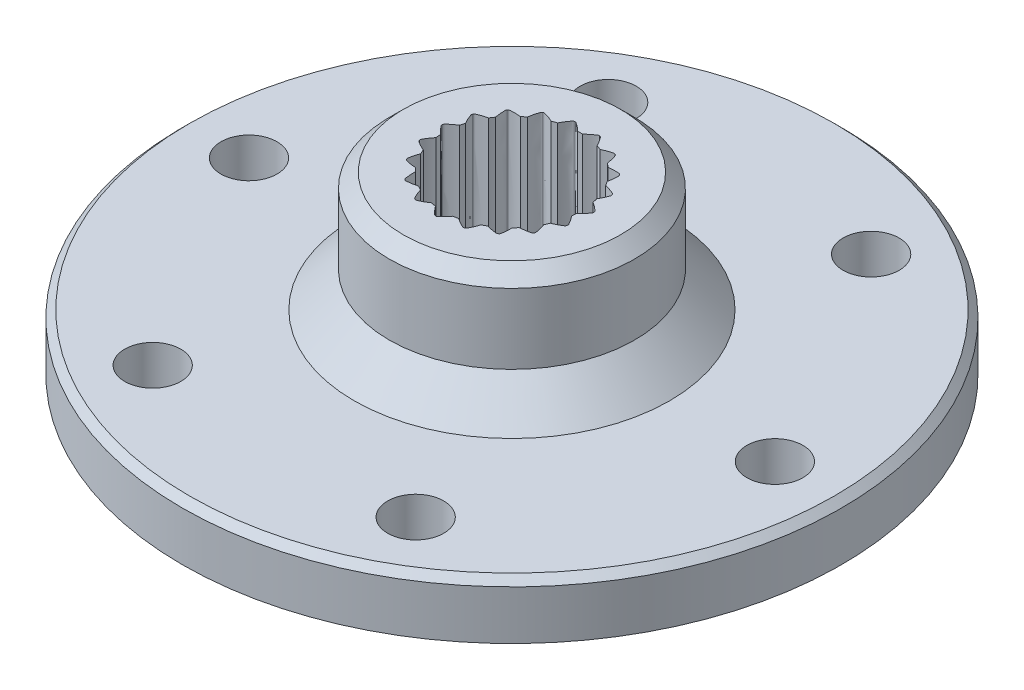
SolidWorks part; units mm, degrees
material "AISI 4340 Steel, normalized"
ref_plane "Front Plane" through (0, 0, 0) normal (0, 0, 1) x (1, 0, 0)
ref_plane "Top Plane" through (0, 0, 0) normal (0, 1, 0) x (1, 0, 0)
ref_plane "Right Plane" through (0, 0, 0) normal (1, 0, 0) x (0, 0, -1)
sketch "Sketch1" plane through (0, 0, 0) normal (0, 1, 0) x (1, 0, 0)
  circle A8 centre (0, 0) radius 47
  circle A9 centre (0, 0) radius 28
  circle A11 centre (-18.75, -32.476) radius 4.55
  circle A12 centre (18.75, -32.476) radius 4.55
  circle A13 centre (37.5, 0) radius 4.55
  circle A14 centre (18.75, 32.476) radius 4.55
  circle A15 centre (-18.75, 32.476) radius 4.55
  circle A16 centre (-37.5, 0) radius 4.55
  circle A17 centre (0, 0) radius 37.5 construction
  dimension "D1" = 94
  dimension "D2" = 56
  dimension "D3" = 9.1
  dimension "D5" = 75
  dimension "D4" = 18.75
extrude "Boss-Extrude1" add sketch "Sketch1" along normal blind 8 contours A9 | A8 A16 A15 A14 A13 A12 A11 A9 | A15 | A14 | A13 | A12 | A11 | A16 region at (-45.6706, 0, 0) region at (0, 0, 0) region at (-18.75, 0, 32.476) region at (18.75, 0, 32.476) region at (37.5, 0, 0) region at (18.75, 0, -32.476) region at (-18.75, 0, -32.476)
sketch "Sketch17" plane through (0, 8, 0) normal (0, 1, 0) x (1, 0, 0)
  circle A0 centre (-18.75, -32.476) radius 4.55
  circle A1 centre (18.75, -32.476) radius 4.55
  circle A2 centre (37.5, 0) radius 4.55
  circle A3 centre (18.75, 32.476) radius 4.55
  circle A4 centre (-18.75, 32.476) radius 4.55
  circle A5 centre (-37.5, 0) radius 4.55
  circle A6 centre (0, 0) radius 37.5 construction
  circle A7 centre (0, 0) radius 47 construction
  point P1 (-37.5, 0)
  point P2 (-18.75, -32.476)
  point P3 (18.75, -32.476)
  point P4 (37.5, 0)
  point P5 (18.75, 32.476)
  point P6 (-18.75, 32.476)
  dimension "D1" = 9.1
  dimension "D2" = 75
  dimension "D3" = 18.75
  dimension "D4" = 37.5
hole_wizard "Ø8.0mm Dowel Hole1" positions "Sketch17" profile "Sketch18" hole size "Ø8.0" standard "DIN" end condition through all
sketch "Sketch18" plane through (-18.75, 8, -32.476) normal (1, 0, 0) x (0, 0, 1)
  line L0 (0, 0) -> (0, 8)
  line L1 (0, 8) -> (4, 8)
  line L2 (4, 8) -> (4, 0)
  line L5 (4, 0) -> (0, 0)
  line L11 (0, -6.35) -> (0, 107.95) construction
  dimension "Thru Hole Dia." = 8
  dimension "Thru Hole Depth" = 8
sketch "Sketch12" plane through (0, 8, 0) normal (0, 1, 0) x (1, 0, 0)
  circle A0 centre (0, 0) radius 17.5
  dimension "D1" = 35
extrude "Boss-Extrude5" add sketch "Sketch12" along normal blind 17 contours A0
sketch "Sketch13" plane through (0, 0, 0) normal (0, -1, 0) x (1, 0, 0)
  circle A0 centre (0, 0) radius 28
  dimension "D1" = 56
extrude "Boss-Extrude6" add sketch "Sketch13" along normal blind 5.08
sketch "Sketch16" plane through (0, 0, 0) normal (0, 1, 0) x (1, 0, 0)
  line B0 (1.8668, 11.187) -> (2.1421, 11.1376)
  line B1 (2.1421, 11.1376) -> (2.416, 11.0814)
  line B2 (2.416, 11.0814) -> (2.491, 11.1676)
  line B3 (2.491, 11.1676) -> (2.5708, 11.2556)
  line B4 (2.5708, 11.2556) -> (2.6534, 11.343)
  line B5 (2.6534, 11.343) -> (2.7388, 11.4297)
  line B6 (2.7388, 11.4297) -> (2.8266, 11.5155)
  line B7 (2.8266, 11.5155) -> (2.9189, 11.6021)
  line B8 (2.9189, 11.6021) -> (3.0133, 11.6874)
  line B9 (3.0133, 11.6874) -> (3.1122, 11.7733)
  line B10 (3.1122, 11.7733) -> (3.2129, 11.8575)
  line B11 (3.2129, 11.8575) -> (3.3178, 11.942)
  line B12 (3.3178, 11.942) -> (3.4243, 12.0245)
  line B13 (3.4243, 12.0245) -> (3.5292, 12.1028)
  line B14 (3.5292, 12.1028) -> (3.5601, 12.1214)
  line B15 (3.5601, 12.1214) -> (3.594, 12.1339)
  line B16 (3.594, 12.1339) -> (3.6296, 12.14)
  line B17 (3.6296, 12.14) -> (3.6657, 12.1394)
  line B18 (3.6657, 12.1394) -> (3.701, 12.1321)
  line B19 (3.701, 12.1321) -> (3.9104, 12.0662)
  line B20 (3.9104, 12.0662) -> (4.1185, 11.9968)
  line B21 (4.1185, 11.9968) -> (4.3254, 11.9237)
  line B22 (4.3254, 11.9237) -> (4.531, 11.8471)
  line B23 (4.531, 11.8471) -> (4.5634, 11.8312)
  line B24 (4.5634, 11.8312) -> (4.5923, 11.8095)
  line B25 (4.5923, 11.8095) -> (4.6167, 11.7829)
  line B26 (4.6167, 11.7829) -> (4.6357, 11.7522)
  line B27 (4.6357, 11.7522) -> (4.6487, 11.7185)
  line B28 (4.6487, 11.7185) -> (4.6833, 11.5923)
  line B29 (4.6833, 11.5923) -> (4.7167, 11.4617)
  line B30 (4.7167, 11.4617) -> (4.7476, 11.3306)
  line B31 (4.7476, 11.3306) -> (4.7754, 11.2023)
  line B32 (4.7754, 11.2023) -> (4.8006, 11.0738)
  line B33 (4.8006, 11.0738) -> (4.8228, 10.9485)
  line B34 (4.8228, 10.9485) -> (4.8424, 10.8235)
  line B35 (4.8424, 10.8235) -> (4.859, 10.7019)
  line B36 (4.859, 10.7019) -> (4.8731, 10.581)
  line B37 (4.8731, 10.581) -> (4.8846, 10.4612)
  line B38 (4.8846, 10.4612) -> (4.8935, 10.3428)
  line B39 (4.8935, 10.3428) -> (4.8997, 10.2287)
  line B40 (4.8997, 10.2287) -> (5.1505, 10.1048)
  line B41 (5.1505, 10.1048) -> (5.398, 9.9747)
  line B42 (5.398, 9.9747) -> (5.6424, 9.8386)
  line B43 (5.6424, 9.8386) -> (5.8832, 9.6965)
  line B44 (5.8832, 9.6965) -> (5.9822, 9.7537)
  line B45 (5.9822, 9.7537) -> (6.0861, 9.811)
  line B46 (6.0861, 9.811) -> (6.1927, 9.8669)
  line B47 (6.1927, 9.8669) -> (6.3016, 9.9212)
  line B48 (6.3016, 9.9212) -> (6.4125, 9.9737)
  line B49 (6.4125, 9.9737) -> (6.5279, 10.0257)
  line B50 (6.5279, 10.0257) -> (6.645, 10.0757)
  line B51 (6.645, 10.0757) -> (6.7663, 10.1248)
  line B52 (6.7663, 10.1248) -> (6.8889, 10.1718)
  line B53 (6.8889, 10.1718) -> (7.0156, 10.2176)
  line B54 (7.0156, 10.2176) -> (7.1431, 10.2611)
  line B55 (7.1431, 10.2611) -> (7.2677, 10.3012)
  line B56 (7.2677, 10.3012) -> (7.303, 10.3087)
  line B57 (7.303, 10.3087) -> (7.3391, 10.3095)
  line B58 (7.3391, 10.3095) -> (7.3748, 10.3037)
  line B59 (7.3748, 10.3037) -> (7.4087, 10.2914)
  line B60 (7.4087, 10.2914) -> (7.4398, 10.273)
  line B61 (7.4398, 10.273) -> (7.6164, 10.1428)
  line B62 (7.6164, 10.1428) -> (7.7907, 10.0095)
  line B63 (7.7907, 10.0095) -> (7.9627, 9.8732)
  line B64 (7.9627, 9.8732) -> (8.1323, 9.734)
  line B65 (8.1323, 9.734) -> (8.1577, 9.7084)
  line B66 (8.1577, 9.7084) -> (8.178, 9.6785)
  line B67 (8.178, 9.6785) -> (8.1924, 9.6454)
  line B68 (8.1924, 9.6454) -> (8.2004, 9.6102)
  line B69 (8.2004, 9.6102) -> (8.2018, 9.5741)
  line B70 (8.2018, 9.5741) -> (8.1936, 9.4435)
  line B71 (8.1936, 9.4435) -> (8.1827, 9.3092)
  line B72 (8.1827, 9.3092) -> (8.1694, 9.1751)
  line B73 (8.1694, 9.1751) -> (8.154, 9.0448)
  line B74 (8.154, 9.0448) -> (8.1362, 8.9151)
  line B75 (8.1362, 8.9151) -> (8.1164, 8.7894)
  line B76 (8.1164, 8.7894) -> (8.0944, 8.6647)
  line B77 (8.0944, 8.6647) -> (8.0706, 8.5443)
  line B78 (8.0706, 8.5443) -> (8.0447, 8.4254)
  line B79 (8.0447, 8.4254) -> (8.0167, 8.3084)
  line B80 (8.0167, 8.3084) -> (7.9867, 8.1935)
  line B81 (7.9867, 8.1935) -> (7.9555, 8.0835)
  line B82 (7.9555, 8.0835) -> (8.1524, 7.8849)
  line B83 (8.1524, 7.8849) -> (8.3443, 7.6815)
  line B84 (8.3443, 7.6815) -> (8.5312, 7.4734)
  line B85 (8.5312, 7.4734) -> (8.7129, 7.2608)
  line B86 (8.7129, 7.2608) -> (8.8251, 7.2828)
  line B87 (8.8251, 7.2828) -> (8.942, 7.3032)
  line B88 (8.942, 7.3032) -> (9.061, 7.3215)
  line B89 (9.061, 7.3215) -> (9.1816, 7.3375)
  line B90 (9.1816, 7.3375) -> (9.3035, 7.3512)
  line B91 (9.3035, 7.3512) -> (9.4296, 7.3629)
  line B92 (9.4296, 7.3629) -> (9.5565, 7.3722)
  line B93 (9.5565, 7.3722) -> (9.6872, 7.3792)
  line B94 (9.6872, 7.3792) -> (9.8184, 7.3838)
  line B95 (9.8184, 7.3838) -> (9.9531, 7.386)
  line B96 (9.9531, 7.386) -> (10.0879, 7.3858)
  line B97 (10.0879, 7.3858) -> (10.2187, 7.3832)
  line B98 (10.2187, 7.3832) -> (10.2546, 7.3788)
  line B99 (10.2546, 7.3788) -> (10.289, 7.3679)
  line B100 (10.289, 7.3679) -> (10.3208, 7.3508)
  line B101 (10.3208, 7.3508) -> (10.3489, 7.3282)
  line B102 (10.3489, 7.3282) -> (10.3723, 7.3007)
  line B103 (10.3723, 7.3007) -> (10.4971, 7.1202)
  line B104 (10.4971, 7.1202) -> (10.6187, 6.9375)
  line B105 (10.6187, 6.9375) -> (10.7371, 6.7528)
  line B106 (10.7371, 6.7528) -> (10.8523, 6.566)
  line B107 (10.8523, 6.566) -> (10.868, 6.5336)
  line B108 (10.868, 6.5336) -> (10.8775, 6.4987)
  line B109 (10.8775, 6.4987) -> (10.8804, 6.4627)
  line B110 (10.8804, 6.4627) -> (10.8765, 6.4268)
  line B111 (10.8765, 6.4268) -> (10.8661, 6.3922)
  line B112 (10.8661, 6.3922) -> (10.8159, 6.2714)
  line B113 (10.8159, 6.2714) -> (10.7621, 6.1479)
  line B114 (10.7621, 6.1479) -> (10.7059, 6.0254)
  line B115 (10.7059, 6.0254) -> (10.649, 5.9071)
  line B116 (10.649, 5.9071) -> (10.59, 5.7902)
  line B117 (10.59, 5.7902) -> (10.5305, 5.6777)
  line B118 (10.5305, 5.6777) -> (10.4692, 5.567)
  line B119 (10.4692, 5.567) -> (10.4077, 5.4608)
  line B120 (10.4077, 5.4608) -> (10.3446, 5.3568)
  line B121 (10.3446, 5.3568) -> (10.2801, 5.2552)
  line B122 (10.2801, 5.2552) -> (10.2144, 5.1563)
  line B123 (10.2144, 5.1563) -> (10.1492, 5.0624)
  line B124 (10.1492, 5.0624) -> (10.2709, 4.8106)
  line B125 (10.2709, 4.8106) -> (10.3864, 4.5559)
  line B126 (10.3864, 4.5559) -> (10.4956, 4.2984)
  line B127 (10.4956, 4.2984) -> (10.5984, 4.0383)
  line B128 (10.5984, 4.0383) -> (10.7116, 4.0227)
  line B129 (10.7116, 4.0227) -> (10.8289, 4.0041)
  line B130 (10.8289, 4.0041) -> (10.9473, 3.9827)
  line B131 (10.9473, 3.9827) -> (11.0666, 3.9587)
  line B132 (11.0666, 3.9587) -> (11.1864, 3.932)
  line B133 (11.1864, 3.932) -> (11.3094, 3.9022)
  line B134 (11.3094, 3.9022) -> (11.4324, 3.8697)
  line B135 (11.4324, 3.8697) -> (11.5584, 3.834)
  line B136 (11.5584, 3.834) -> (11.684, 3.7957)
  line B137 (11.684, 3.7957) -> (11.8121, 3.7541)
  line B138 (11.8121, 3.7541) -> (11.9394, 3.7101)
  line B139 (11.9394, 3.7101) -> (12.0624, 3.6651)
  line B140 (12.0624, 3.6651) -> (12.0948, 3.6494)
  line B141 (12.0948, 3.6494) -> (12.1238, 3.6279)
  line B142 (12.1238, 3.6279) -> (12.1484, 3.6014)
  line B143 (12.1484, 3.6014) -> (12.1676, 3.5708)
  line B144 (12.1676, 3.5708) -> (12.1808, 3.5372)
  line B145 (12.1808, 3.5372) -> (12.2402, 3.326)
  line B146 (12.2402, 3.326) -> (12.2959, 3.1137)
  line B147 (12.2959, 3.1137) -> (12.3479, 2.9006)
  line B148 (12.3479, 2.9006) -> (12.3963, 2.6865)
  line B149 (12.3963, 2.6865) -> (12.4006, 2.6507)
  line B150 (12.4006, 2.6507) -> (12.3983, 2.6147)
  line B151 (12.3983, 2.6147) -> (12.3893, 2.5797)
  line B152 (12.3893, 2.5797) -> (12.374, 2.547)
  line B153 (12.374, 2.547) -> (12.3529, 2.5177)
  line B154 (12.3529, 2.5177) -> (12.2662, 2.4196)
  line B155 (12.2662, 2.4196) -> (12.1752, 2.3203)
  line B156 (12.1752, 2.3203) -> (12.0823, 2.2227)
  line B157 (12.0823, 2.2227) -> (11.9901, 2.1293)
  line B158 (11.9901, 2.1293) -> (11.8963, 2.0379)
  line B159 (11.8963, 2.0379) -> (11.8035, 1.9508)
  line B160 (11.8035, 1.9508) -> (11.7096, 1.866)
  line B161 (11.7096, 1.866) -> (11.6169, 1.7856)
  line B162 (11.6169, 1.7856) -> (11.5234, 1.7077)
  line B163 (11.5234, 1.7077) -> (11.4294, 1.6325)
  line B164 (11.4294, 1.6325) -> (11.3352, 1.5603)
  line B165 (11.3352, 1.5603) -> (11.243, 1.4927)
  line B166 (11.243, 1.4927) -> (11.2764, 1.215)
  line B167 (11.2764, 1.215) -> (11.3029, 0.9366)
  line B168 (11.3029, 0.9366) -> (11.3226, 0.6576)
  line B169 (11.3226, 0.6576) -> (11.3354, 0.3782)
  line B170 (11.3354, 0.3782) -> (11.4374, 0.3267)
  line B171 (11.4374, 0.3267) -> (11.5422, 0.271)
  line B172 (11.5422, 0.271) -> (11.6473, 0.2123)
  line B173 (11.6473, 0.2123) -> (11.7523, 0.1509)
  line B174 (11.7523, 0.1509) -> (11.857, 0.0868)
  line B175 (11.857, 0.0868) -> (11.9636, 0.0186)
  line B176 (11.9636, 0.0186) -> (12.0695, -0.0521)
  line B177 (12.0695, -0.0521) -> (12.177, -0.1268)
  line B178 (12.177, -0.1268) -> (12.2834, -0.2037)
  line B179 (12.2834, -0.2037) -> (12.391, -0.2847)
  line B180 (12.391, -0.2847) -> (12.4972, -0.3677)
  line B181 (12.4972, -0.3677) -> (12.5988, -0.4501)
  line B182 (12.5988, -0.4501) -> (12.6245, -0.4756)
  line B183 (12.6245, -0.4756) -> (12.6449, -0.5053)
  line B184 (12.6449, -0.5053) -> (12.6595, -0.5383)
  line B185 (12.6595, -0.5383) -> (12.6678, -0.5735)
  line B186 (12.6678, -0.5735) -> (12.6694, -0.6096)
  line B187 (12.6694, -0.6096) -> (12.6569, -0.8286)
  line B188 (12.6569, -0.8286) -> (12.6407, -1.0474)
  line B189 (12.6407, -1.0474) -> (12.6207, -1.2659)
  line B190 (12.6207, -1.2659) -> (12.5969, -1.4841)
  line B191 (12.5969, -1.4841) -> (12.5894, -1.5194)
  line B192 (12.5894, -1.5194) -> (12.5755, -1.5527)
  line B193 (12.5755, -1.5527) -> (12.5556, -1.5829)
  line B194 (12.5556, -1.5829) -> (12.5305, -1.6088)
  line B195 (12.5305, -1.6088) -> (12.5011, -1.6297)
  line B196 (12.5011, -1.6297) -> (12.3872, -1.6943)
  line B197 (12.3872, -1.6943) -> (12.2689, -1.7587)
  line B198 (12.2689, -1.7587) -> (12.1494, -1.8208)
  line B199 (12.1494, -1.8208) -> (12.0318, -1.8792)
  line B200 (12.0318, -1.8792) -> (11.9135, -1.9352)
  line B201 (11.9135, -1.9352) -> (11.7974, -1.9875)
  line B202 (11.7974, -1.9875) -> (11.681, -2.0372)
  line B203 (11.681, -2.0372) -> (11.5672, -2.0832)
  line B204 (11.5672, -2.0832) -> (11.4535, -2.1265)
  line B205 (11.4535, -2.1265) -> (11.3402, -2.1671)
  line B206 (11.3402, -2.1671) -> (11.2277, -2.2048)
  line B207 (11.2277, -2.2048) -> (11.1185, -2.2388)
  line B208 (11.1185, -2.2388) -> (11.0599, -2.5123)
  line B209 (11.0599, -2.5123) -> (10.9946, -2.7842)
  line B210 (10.9946, -2.7842) -> (10.9226, -3.0545)
  line B211 (10.9226, -3.0545) -> (10.844, -3.3229)
  line B212 (10.844, -3.3229) -> (10.9238, -3.4047)
  line B213 (10.9238, -3.4047) -> (11.0048, -3.4915)
  line B214 (11.0048, -3.4915) -> (11.0852, -3.5811)
  line B215 (11.0852, -3.5811) -> (11.1645, -3.6733)
  line B216 (11.1645, -3.6733) -> (11.2427, -3.7679)
  line B217 (11.2427, -3.7679) -> (11.3214, -3.867)
  line B218 (11.3214, -3.867) -> (11.3986, -3.9682)
  line B219 (11.3986, -3.9682) -> (11.4761, -4.0738)
  line B220 (11.4761, -4.0738) -> (11.5517, -4.1811)
  line B221 (11.5517, -4.1811) -> (11.6272, -4.2927)
  line B222 (11.6272, -4.2927) -> (11.7007, -4.4056)
  line B223 (11.7007, -4.4056) -> (11.7701, -4.5165)
  line B224 (11.7701, -4.5165) -> (11.786, -4.5489)
  line B225 (11.786, -4.5489) -> (11.7957, -4.5837)
  line B226 (11.7957, -4.5837) -> (11.7988, -4.6197)
  line B227 (11.7988, -4.6197) -> (11.7952, -4.6556)
  line B228 (11.7952, -4.6556) -> (11.785, -4.6903)
  line B229 (11.785, -4.6903) -> (11.7021, -4.8934)
  line B230 (11.7021, -4.8934) -> (11.6157, -5.0951)
  line B231 (11.6157, -5.0951) -> (11.5258, -5.2953)
  line B232 (11.5258, -5.2953) -> (11.4325, -5.4939)
  line B233 (11.4325, -5.4939) -> (11.4139, -5.5248)
  line B234 (11.4139, -5.5248) -> (11.3899, -5.5518)
  line B235 (11.3899, -5.5518) -> (11.3614, -5.5739)
  line B236 (11.3614, -5.5739) -> (11.3292, -5.5903)
  line B237 (11.3292, -5.5903) -> (11.2946, -5.6005)
  line B238 (11.2946, -5.6005) -> (11.1659, -5.6246)
  line B239 (11.1659, -5.6246) -> (11.0331, -5.6471)
  line B240 (11.0331, -5.6471) -> (10.8998, -5.6671)
  line B241 (10.8998, -5.6671) -> (10.7697, -5.6841)
  line B242 (10.7697, -5.6841) -> (10.6396, -5.6987)
  line B243 (10.6396, -5.6987) -> (10.5129, -5.7104)
  line B244 (10.5129, -5.7104) -> (10.3866, -5.7196)
  line B245 (10.3866, -5.7196) -> (10.2641, -5.7262)
  line B246 (10.2641, -5.7262) -> (10.1425, -5.7302)
  line B247 (10.1425, -5.7302) -> (10.0221, -5.7318)
  line B248 (10.0221, -5.7318) -> (9.9034, -5.7309)
  line B249 (9.9034, -5.7309) -> (9.7892, -5.7277)
  line B250 (9.7892, -5.7277) -> (9.6449, -5.9673)
  line B251 (9.6449, -5.9673) -> (9.4949, -6.2033)
  line B252 (9.4949, -6.2033) -> (9.339, -6.4355)
  line B253 (9.339, -6.4355) -> (9.1775, -6.6639)
  line B254 (9.1775, -6.6639) -> (9.2264, -6.7672)
  line B255 (9.2264, -6.7672) -> (9.2749, -6.8755)
  line B256 (9.2749, -6.8755) -> (9.3218, -6.9864)
  line B257 (9.3218, -6.9864) -> (9.3669, -7.0994)
  line B258 (9.3669, -7.0994) -> (9.4101, -7.2142)
  line B259 (9.4101, -7.2142) -> (9.4524, -7.3336)
  line B260 (9.4524, -7.3336) -> (9.4926, -7.4543)
  line B261 (9.4926, -7.4543) -> (9.5315, -7.5793)
  line B262 (9.5315, -7.5793) -> (9.5682, -7.7054)
  line B263 (9.5682, -7.7054) -> (9.6034, -7.8354)
  line B264 (9.6034, -7.8354) -> (9.6362, -7.9661)
  line B265 (9.6362, -7.9661) -> (9.6658, -8.0936)
  line B266 (9.6658, -8.0936) -> (9.6704, -8.1294)
  line B267 (9.6704, -8.1294) -> (9.6682, -8.1654)
  line B268 (9.6682, -8.1654) -> (9.6595, -8.2005)
  line B269 (9.6595, -8.2005) -> (9.6444, -8.2333)
  line B270 (9.6444, -8.2333) -> (9.6235, -8.2627)
  line B271 (9.6235, -8.2627) -> (9.4792, -8.428)
  line B272 (9.4792, -8.428) -> (9.332, -8.5907)
  line B273 (9.332, -8.5907) -> (9.182, -8.7508)
  line B274 (9.182, -8.7508) -> (9.0292, -8.9083)
  line B275 (9.0292, -8.9083) -> (9.0016, -8.9316)
  line B276 (9.0016, -8.9316) -> (8.9701, -8.9493)
  line B277 (8.9701, -8.9493) -> (8.9359, -8.9609)
  line B278 (8.9359, -8.9609) -> (8.9002, -8.966)
  line B279 (8.9002, -8.966) -> (8.8641, -8.9644)
  line B280 (8.8641, -8.9644) -> (8.7346, -8.9454)
  line B281 (8.7346, -8.9454) -> (8.6017, -8.9235)
  line B282 (8.6017, -8.9235) -> (8.4692, -8.8992)
  line B283 (8.4692, -8.8992) -> (8.3405, -8.8731)
  line B284 (8.3405, -8.8731) -> (8.2127, -8.8446)
  line B285 (8.2127, -8.8446) -> (8.0891, -8.8145)
  line B286 (8.0891, -8.8145) -> (7.9667, -8.7822)
  line B287 (7.9667, -8.7822) -> (7.8486, -8.7486)
  line B288 (7.8486, -8.7486) -> (7.7323, -8.713)
  line B289 (7.7323, -8.713) -> (7.618, -8.6754)
  line B290 (7.618, -8.6754) -> (7.506, -8.6361)
  line B291 (7.506, -8.6361) -> (7.399, -8.5959)
  line B292 (7.399, -8.5959) -> (7.1848, -8.7757)
  line B293 (7.1848, -8.7757) -> (6.9662, -8.9502)
  line B294 (6.9662, -8.9502) -> (6.7434, -9.1192)
  line B295 (6.7434, -9.1192) -> (6.5165, -9.2827)
  line B296 (6.5165, -9.2827) -> (6.5292, -9.3963)
  line B297 (6.5292, -9.3963) -> (6.5399, -9.5146)
  line B298 (6.5399, -9.5146) -> (6.5482, -9.6346)
  line B299 (6.5482, -9.6346) -> (6.5542, -9.7561)
  line B300 (6.5542, -9.7561) -> (6.5578, -9.8788)
  line B301 (6.5578, -9.8788) -> (6.559, -10.0054)
  line B302 (6.559, -10.0054) -> (6.5578, -10.1327)
  line B303 (6.5578, -10.1327) -> (6.5541, -10.2635)
  line B304 (6.5541, -10.2635) -> (6.5478, -10.3946)
  line B305 (6.5478, -10.3946) -> (6.5389, -10.5291)
  line B306 (6.5389, -10.5291) -> (6.5275, -10.6633)
  line B307 (6.5275, -10.6633) -> (6.5141, -10.7935)
  line B308 (6.5141, -10.7935) -> (6.5068, -10.8289)
  line B309 (6.5068, -10.8289) -> (6.4931, -10.8623)
  line B310 (6.4931, -10.8623) -> (6.4734, -10.8926)
  line B311 (6.4734, -10.8926) -> (6.4485, -10.9187)
  line B312 (6.4485, -10.9187) -> (6.4192, -10.9398)
  line B313 (6.4192, -10.9398) -> (6.229, -11.0492)
  line B314 (6.229, -11.0492) -> (6.0369, -11.1553)
  line B315 (6.0369, -11.1553) -> (5.8431, -11.258)
  line B316 (5.8431, -11.258) -> (5.6474, -11.3574)
  line B317 (5.6474, -11.3574) -> (5.6138, -11.3704)
  line B318 (5.6138, -11.3704) -> (5.5783, -11.377)
  line B319 (5.5783, -11.377) -> (5.5421, -11.3769)
  line B320 (5.5421, -11.3769) -> (5.5067, -11.3701)
  line B321 (5.5067, -11.3701) -> (5.4731, -11.3569)
  line B322 (5.4731, -11.3569) -> (5.3568, -11.2969)
  line B323 (5.3568, -11.2969) -> (5.2382, -11.233)
  line B324 (5.2382, -11.233) -> (5.1207, -11.1669)
  line B325 (5.1207, -11.1669) -> (5.0075, -11.1005)
  line B326 (5.0075, -11.1005) -> (4.8959, -11.032)
  line B327 (4.8959, -11.032) -> (4.7887, -10.9634)
  line B328 (4.7887, -10.9634) -> (4.6834, -10.8932)
  line B329 (4.6834, -10.8932) -> (4.5827, -10.8231)
  line B330 (4.5827, -10.8231) -> (4.4842, -10.7516)
  line B331 (4.4842, -10.7516) -> (4.3883, -10.6789)
  line B332 (4.3883, -10.6789) -> (4.2952, -10.6053)
  line B333 (4.2952, -10.6053) -> (4.207, -10.5326)
  line B334 (4.207, -10.5326) -> (3.946, -10.6331)
  line B335 (3.946, -10.6331) -> (3.6826, -10.7272)
  line B336 (3.6826, -10.7272) -> (3.417, -10.8147)
  line B337 (3.417, -10.8147) -> (3.1493, -10.8957)
  line B338 (3.1493, -10.8957) -> (3.1244, -11.0072)
  line B339 (3.1244, -11.0072) -> (3.0962, -11.1225)
  line B340 (3.0962, -11.1225) -> (3.0651, -11.2388)
  line B341 (3.0651, -11.2388) -> (3.0313, -11.3557)
  line B342 (3.0313, -11.3557) -> (2.9948, -11.4729)
  line B343 (2.9948, -11.4729) -> (2.9549, -11.593)
  line B344 (2.9549, -11.593) -> (2.9124, -11.713)
  line B345 (2.9124, -11.713) -> (2.8664, -11.8355)
  line B346 (2.8664, -11.8355) -> (2.8179, -11.9575)
  line B347 (2.8179, -11.9575) -> (2.7658, -12.0818)
  line B348 (2.7658, -12.0818) -> (2.7114, -12.205)
  line B349 (2.7114, -12.205) -> (2.6565, -12.3238)
  line B350 (2.6565, -12.3238) -> (2.6381, -12.3549)
  line B351 (2.6381, -12.3549) -> (2.6143, -12.382)
  line B352 (2.6143, -12.382) -> (2.5859, -12.4043)
  line B353 (2.5859, -12.4043) -> (2.5538, -12.4209)
  line B354 (2.5538, -12.4209) -> (2.5193, -12.4313)
  line B355 (2.5193, -12.4313) -> (2.3038, -12.4731)
  line B356 (2.3038, -12.4731) -> (2.0877, -12.5111)
  line B357 (2.0877, -12.5111) -> (1.871, -12.5453)
  line B358 (1.871, -12.5453) -> (1.6537, -12.5758)
  line B359 (1.6537, -12.5758) -> (1.6176, -12.5771)
  line B360 (1.6176, -12.5771) -> (1.5819, -12.5718)
  line B361 (1.5819, -12.5718) -> (1.5478, -12.56)
  line B362 (1.5478, -12.56) -> (1.5165, -12.5421)
  line B363 (1.5165, -12.5421) -> (1.489, -12.5186)
  line B364 (1.489, -12.5186) -> (1.3984, -12.4241)
  line B365 (1.3984, -12.4241) -> (1.307, -12.3252)
  line B366 (1.307, -12.3252) -> (1.2174, -12.2246)
  line B367 (1.2174, -12.2246) -> (1.1319, -12.125)
  line B368 (1.1319, -12.125) -> (1.0486, -12.024)
  line B369 (1.0486, -12.024) -> (0.9694, -11.9243)
  line B370 (0.9694, -11.9243) -> (0.8927, -11.8237)
  line B371 (0.8927, -11.8237) -> (0.8202, -11.7246)
  line B372 (0.8202, -11.7246) -> (0.7502, -11.6251)
  line B373 (0.7502, -11.6251) -> (0.6831, -11.5252)
  line B374 (0.6831, -11.5252) -> (0.6189, -11.4253)
  line B375 (0.6189, -11.4253) -> (0.5591, -11.3279)
  line B376 (0.5591, -11.3279) -> (0.2797, -11.3382)
  line B377 (0.2797, -11.3382) -> (0, -11.3417)
  line B378 (0, -11.3417) -> (-0.2797, -11.3382)
  line B379 (-0.2797, -11.3382) -> (-0.5591, -11.3279)
  line B380 (-0.5591, -11.3279) -> (-0.6189, -11.4253)
  line B381 (-0.6189, -11.4253) -> (-0.6831, -11.5252)
  line B382 (-0.6831, -11.5252) -> (-0.7502, -11.6251)
  line B383 (-0.7502, -11.6251) -> (-0.8202, -11.7246)
  line B384 (-0.8202, -11.7246) -> (-0.8927, -11.8237)
  line B385 (-0.8927, -11.8237) -> (-0.9694, -11.9243)
  line B386 (-0.9694, -11.9243) -> (-1.0486, -12.024)
  line B387 (-1.0486, -12.024) -> (-1.1319, -12.125)
  line B388 (-1.1319, -12.125) -> (-1.2174, -12.2246)
  line B389 (-1.2174, -12.2246) -> (-1.307, -12.3252)
  line B390 (-1.307, -12.3252) -> (-1.3984, -12.4241)
  line B391 (-1.3984, -12.4241) -> (-1.489, -12.5186)
  line B392 (-1.489, -12.5186) -> (-1.5165, -12.5421)
  line B393 (-1.5165, -12.5421) -> (-1.5478, -12.56)
  line B394 (-1.5478, -12.56) -> (-1.5819, -12.5718)
  line B395 (-1.5819, -12.5718) -> (-1.6176, -12.5771)
  line B396 (-1.6176, -12.5771) -> (-1.6537, -12.5758)
  line B397 (-1.6537, -12.5758) -> (-1.871, -12.5453)
  line B398 (-1.871, -12.5453) -> (-2.0877, -12.5111)
  line B399 (-2.0877, -12.5111) -> (-2.3038, -12.4731)
  line B400 (-2.3038, -12.4731) -> (-2.5193, -12.4313)
  line B401 (-2.5193, -12.4313) -> (-2.5538, -12.4209)
  line B402 (-2.5538, -12.4209) -> (-2.5859, -12.4043)
  line B403 (-2.5859, -12.4043) -> (-2.6143, -12.382)
  line B404 (-2.6143, -12.382) -> (-2.6381, -12.3549)
  line B405 (-2.6381, -12.3549) -> (-2.6565, -12.3238)
  line B406 (-2.6565, -12.3238) -> (-2.7114, -12.205)
  line B407 (-2.7114, -12.205) -> (-2.7658, -12.0818)
  line B408 (-2.7658, -12.0818) -> (-2.8179, -11.9575)
  line B409 (-2.8179, -11.9575) -> (-2.8664, -11.8355)
  line B410 (-2.8664, -11.8355) -> (-2.9124, -11.713)
  line B411 (-2.9124, -11.713) -> (-2.9549, -11.593)
  line B412 (-2.9549, -11.593) -> (-2.9948, -11.4729)
  line B413 (-2.9948, -11.4729) -> (-3.0313, -11.3557)
  line B414 (-3.0313, -11.3557) -> (-3.0651, -11.2388)
  line B415 (-3.0651, -11.2388) -> (-3.0962, -11.1225)
  line B416 (-3.0962, -11.1225) -> (-3.1244, -11.0072)
  line B417 (-3.1244, -11.0072) -> (-3.1493, -10.8957)
  line B418 (-3.1493, -10.8957) -> (-3.417, -10.8147)
  line B419 (-3.417, -10.8147) -> (-3.6826, -10.7272)
  line B420 (-3.6826, -10.7272) -> (-3.946, -10.6331)
  line B421 (-3.946, -10.6331) -> (-4.207, -10.5326)
  line B422 (-4.207, -10.5326) -> (-4.2952, -10.6053)
  line B423 (-4.2952, -10.6053) -> (-4.3883, -10.6789)
  line B424 (-4.3883, -10.6789) -> (-4.4842, -10.7516)
  line B425 (-4.4842, -10.7516) -> (-4.5827, -10.8231)
  line B426 (-4.5827, -10.8231) -> (-4.6834, -10.8932)
  line B427 (-4.6834, -10.8932) -> (-4.7887, -10.9634)
  line B428 (-4.7887, -10.9634) -> (-4.8959, -11.032)
  line B429 (-4.8959, -11.032) -> (-5.0075, -11.1005)
  line B430 (-5.0075, -11.1005) -> (-5.1207, -11.1669)
  line B431 (-5.1207, -11.1669) -> (-5.2382, -11.233)
  line B432 (-5.2382, -11.233) -> (-5.3568, -11.2969)
  line B433 (-5.3568, -11.2969) -> (-5.4731, -11.3569)
  line B434 (-5.4731, -11.3569) -> (-5.5067, -11.3701)
  line B435 (-5.5067, -11.3701) -> (-5.5421, -11.3769)
  line B436 (-5.5421, -11.3769) -> (-5.5783, -11.377)
  line B437 (-5.5783, -11.377) -> (-5.6138, -11.3704)
  line B438 (-5.6138, -11.3704) -> (-5.6474, -11.3574)
  line B439 (-5.6474, -11.3574) -> (-5.8431, -11.258)
  line B440 (-5.8431, -11.258) -> (-6.0369, -11.1553)
  line B441 (-6.0369, -11.1553) -> (-6.229, -11.0492)
  line B442 (-6.229, -11.0492) -> (-6.4192, -10.9398)
  line B443 (-6.4192, -10.9398) -> (-6.4485, -10.9187)
  line B444 (-6.4485, -10.9187) -> (-6.4734, -10.8926)
  line B445 (-6.4734, -10.8926) -> (-6.4931, -10.8623)
  line B446 (-6.4931, -10.8623) -> (-6.5068, -10.8289)
  line B447 (-6.5068, -10.8289) -> (-6.5141, -10.7935)
  line B448 (-6.5141, -10.7935) -> (-6.5275, -10.6633)
  line B449 (-6.5275, -10.6633) -> (-6.5389, -10.5291)
  line B450 (-6.5389, -10.5291) -> (-6.5478, -10.3946)
  line B451 (-6.5478, -10.3946) -> (-6.5541, -10.2635)
  line B452 (-6.5541, -10.2635) -> (-6.5578, -10.1327)
  line B453 (-6.5578, -10.1327) -> (-6.559, -10.0054)
  line B454 (-6.559, -10.0054) -> (-6.5578, -9.8788)
  line B455 (-6.5578, -9.8788) -> (-6.5542, -9.7561)
  line B456 (-6.5542, -9.7561) -> (-6.5482, -9.6346)
  line B457 (-6.5482, -9.6346) -> (-6.5399, -9.5146)
  line B458 (-6.5399, -9.5146) -> (-6.5292, -9.3963)
  line B459 (-6.5292, -9.3963) -> (-6.5165, -9.2827)
  line B460 (-6.5165, -9.2827) -> (-6.7434, -9.1192)
  line B461 (-6.7434, -9.1192) -> (-6.9662, -8.9502)
  line B462 (-6.9662, -8.9502) -> (-7.1848, -8.7757)
  line B463 (-7.1848, -8.7757) -> (-7.399, -8.5959)
  line B464 (-7.399, -8.5959) -> (-7.506, -8.6361)
  line B465 (-7.506, -8.6361) -> (-7.618, -8.6754)
  line B466 (-7.618, -8.6754) -> (-7.7323, -8.713)
  line B467 (-7.7323, -8.713) -> (-7.8486, -8.7486)
  line B468 (-7.8486, -8.7486) -> (-7.9667, -8.7822)
  line B469 (-7.9667, -8.7822) -> (-8.0891, -8.8145)
  line B470 (-8.0891, -8.8145) -> (-8.2127, -8.8446)
  line B471 (-8.2127, -8.8446) -> (-8.3405, -8.8731)
  line B472 (-8.3405, -8.8731) -> (-8.4692, -8.8992)
  line B473 (-8.4692, -8.8992) -> (-8.6017, -8.9235)
  line B474 (-8.6017, -8.9235) -> (-8.7346, -8.9454)
  line B475 (-8.7346, -8.9454) -> (-8.8641, -8.9644)
  line B476 (-8.8641, -8.9644) -> (-8.9002, -8.966)
  line B477 (-8.9002, -8.966) -> (-8.9359, -8.9609)
  line B478 (-8.9359, -8.9609) -> (-8.9701, -8.9493)
  line B479 (-8.9701, -8.9493) -> (-9.0016, -8.9316)
  line B480 (-9.0016, -8.9316) -> (-9.0292, -8.9083)
  line B481 (-9.0292, -8.9083) -> (-9.182, -8.7508)
  line B482 (-9.182, -8.7508) -> (-9.332, -8.5907)
  line B483 (-9.332, -8.5907) -> (-9.4792, -8.428)
  line B484 (-9.4792, -8.428) -> (-9.6235, -8.2627)
  line B485 (-9.6235, -8.2627) -> (-9.6444, -8.2333)
  line B486 (-9.6444, -8.2333) -> (-9.6595, -8.2005)
  line B487 (-9.6595, -8.2005) -> (-9.6682, -8.1654)
  line B488 (-9.6682, -8.1654) -> (-9.6704, -8.1294)
  line B489 (-9.6704, -8.1294) -> (-9.6658, -8.0936)
  line B490 (-9.6658, -8.0936) -> (-9.6362, -7.9661)
  line B491 (-9.6362, -7.9661) -> (-9.6034, -7.8354)
  line B492 (-9.6034, -7.8354) -> (-9.5682, -7.7054)
  line B493 (-9.5682, -7.7054) -> (-9.5315, -7.5793)
  line B494 (-9.5315, -7.5793) -> (-9.4926, -7.4543)
  line B495 (-9.4926, -7.4543) -> (-9.4524, -7.3336)
  line B496 (-9.4524, -7.3336) -> (-9.4101, -7.2142)
  line B497 (-9.4101, -7.2142) -> (-9.3669, -7.0994)
  line B498 (-9.3669, -7.0994) -> (-9.3218, -6.9864)
  line B499 (-9.3218, -6.9864) -> (-9.2749, -6.8755)
  line B500 (-9.2749, -6.8755) -> (-9.2264, -6.7672)
  line B501 (-9.2264, -6.7672) -> (-9.1775, -6.6639)
  line B502 (-9.1775, -6.6639) -> (-9.339, -6.4355)
  line B503 (-9.339, -6.4355) -> (-9.4949, -6.2033)
  line B504 (-9.4949, -6.2033) -> (-9.6449, -5.9673)
  line B505 (-9.6449, -5.9673) -> (-9.7892, -5.7277)
  line B506 (-9.7892, -5.7277) -> (-9.9034, -5.7309)
  line B507 (-9.9034, -5.7309) -> (-10.0221, -5.7318)
  line B508 (-10.0221, -5.7318) -> (-10.1425, -5.7302)
  line B509 (-10.1425, -5.7302) -> (-10.2641, -5.7262)
  line B510 (-10.2641, -5.7262) -> (-10.3866, -5.7196)
  line B511 (-10.3866, -5.7196) -> (-10.5129, -5.7104)
  line B512 (-10.5129, -5.7104) -> (-10.6396, -5.6987)
  line B513 (-10.6396, -5.6987) -> (-10.7697, -5.6841)
  line B514 (-10.7697, -5.6841) -> (-10.8998, -5.6671)
  line B515 (-10.8998, -5.6671) -> (-11.0331, -5.6471)
  line B516 (-11.0331, -5.6471) -> (-11.1659, -5.6246)
  line B517 (-11.1659, -5.6246) -> (-11.2946, -5.6005)
  line B518 (-11.2946, -5.6005) -> (-11.3292, -5.5903)
  line B519 (-11.3292, -5.5903) -> (-11.3614, -5.5739)
  line B520 (-11.3614, -5.5739) -> (-11.3899, -5.5518)
  line B521 (-11.3899, -5.5518) -> (-11.4139, -5.5248)
  line B522 (-11.4139, -5.5248) -> (-11.4325, -5.4939)
  line B523 (-11.4325, -5.4939) -> (-11.5258, -5.2953)
  line B524 (-11.5258, -5.2953) -> (-11.6157, -5.0951)
  line B525 (-11.6157, -5.0951) -> (-11.7021, -4.8934)
  line B526 (-11.7021, -4.8934) -> (-11.785, -4.6903)
  line B527 (-11.785, -4.6903) -> (-11.7952, -4.6556)
  line B528 (-11.7952, -4.6556) -> (-11.7988, -4.6197)
  line B529 (-11.7988, -4.6197) -> (-11.7957, -4.5837)
  line B530 (-11.7957, -4.5837) -> (-11.786, -4.5489)
  line B531 (-11.786, -4.5489) -> (-11.7701, -4.5165)
  line B532 (-11.7701, -4.5165) -> (-11.7007, -4.4056)
  line B533 (-11.7007, -4.4056) -> (-11.6272, -4.2927)
  line B534 (-11.6272, -4.2927) -> (-11.5517, -4.1811)
  line B535 (-11.5517, -4.1811) -> (-11.4761, -4.0738)
  line B536 (-11.4761, -4.0738) -> (-11.3986, -3.9682)
  line B537 (-11.3986, -3.9682) -> (-11.3214, -3.867)
  line B538 (-11.3214, -3.867) -> (-11.2427, -3.7679)
  line B539 (-11.2427, -3.7679) -> (-11.1645, -3.6733)
  line B540 (-11.1645, -3.6733) -> (-11.0852, -3.5811)
  line B541 (-11.0852, -3.5811) -> (-11.0048, -3.4915)
  line B542 (-11.0048, -3.4915) -> (-10.9238, -3.4047)
  line B543 (-10.9238, -3.4047) -> (-10.844, -3.3229)
  line B544 (-10.844, -3.3229) -> (-10.9226, -3.0545)
  line B545 (-10.9226, -3.0545) -> (-10.9946, -2.7842)
  line B546 (-10.9946, -2.7842) -> (-11.0599, -2.5123)
  line B547 (-11.0599, -2.5123) -> (-11.1185, -2.2388)
  line B548 (-11.1185, -2.2388) -> (-11.2277, -2.2048)
  line B549 (-11.2277, -2.2048) -> (-11.3402, -2.1671)
  line B550 (-11.3402, -2.1671) -> (-11.4535, -2.1265)
  line B551 (-11.4535, -2.1265) -> (-11.5672, -2.0832)
  line B552 (-11.5672, -2.0832) -> (-11.681, -2.0372)
  line B553 (-11.681, -2.0372) -> (-11.7974, -1.9875)
  line B554 (-11.7974, -1.9875) -> (-11.9135, -1.9352)
  line B555 (-11.9135, -1.9352) -> (-12.0318, -1.8792)
  line B556 (-12.0318, -1.8792) -> (-12.1494, -1.8208)
  line B557 (-12.1494, -1.8208) -> (-12.2689, -1.7587)
  line B558 (-12.2689, -1.7587) -> (-12.3872, -1.6943)
  line B559 (-12.3872, -1.6943) -> (-12.5011, -1.6297)
  line B560 (-12.5011, -1.6297) -> (-12.5305, -1.6088)
  line B561 (-12.5305, -1.6088) -> (-12.5556, -1.5829)
  line B562 (-12.5556, -1.5829) -> (-12.5755, -1.5527)
  line B563 (-12.5755, -1.5527) -> (-12.5894, -1.5194)
  line B564 (-12.5894, -1.5194) -> (-12.5969, -1.4841)
  line B565 (-12.5969, -1.4841) -> (-12.6207, -1.2659)
  line B566 (-12.6207, -1.2659) -> (-12.6407, -1.0474)
  line B567 (-12.6407, -1.0474) -> (-12.6569, -0.8286)
  line B568 (-12.6569, -0.8286) -> (-12.6694, -0.6096)
  line B569 (-12.6694, -0.6096) -> (-12.6678, -0.5735)
  line B570 (-12.6678, -0.5735) -> (-12.6595, -0.5383)
  line B571 (-12.6595, -0.5383) -> (-12.6449, -0.5053)
  line B572 (-12.6449, -0.5053) -> (-12.6245, -0.4756)
  line B573 (-12.6245, -0.4756) -> (-12.5988, -0.4501)
  line B574 (-12.5988, -0.4501) -> (-12.4972, -0.3677)
  line B575 (-12.4972, -0.3677) -> (-12.391, -0.2847)
  line B576 (-12.391, -0.2847) -> (-12.2834, -0.2037)
  line B577 (-12.2834, -0.2037) -> (-12.177, -0.1268)
  line B578 (-12.177, -0.1268) -> (-12.0695, -0.0521)
  line B579 (-12.0695, -0.0521) -> (-11.9636, 0.0186)
  line B580 (-11.9636, 0.0186) -> (-11.857, 0.0868)
  line B581 (-11.857, 0.0868) -> (-11.7523, 0.1509)
  line B582 (-11.7523, 0.1509) -> (-11.6473, 0.2123)
  line B583 (-11.6473, 0.2123) -> (-11.5422, 0.271)
  line B584 (-11.5422, 0.271) -> (-11.4374, 0.3267)
  line B585 (-11.4374, 0.3267) -> (-11.3354, 0.3782)
  line B586 (-11.3354, 0.3782) -> (-11.3226, 0.6576)
  line B587 (-11.3226, 0.6576) -> (-11.3029, 0.9366)
  line B588 (-11.3029, 0.9366) -> (-11.2764, 1.215)
  line B589 (-11.2764, 1.215) -> (-11.243, 1.4927)
  line B590 (-11.243, 1.4927) -> (-11.3352, 1.5603)
  line B591 (-11.3352, 1.5603) -> (-11.4294, 1.6325)
  line B592 (-11.4294, 1.6325) -> (-11.5234, 1.7077)
  line B593 (-11.5234, 1.7077) -> (-11.6169, 1.7856)
  line B594 (-11.6169, 1.7856) -> (-11.7096, 1.866)
  line B595 (-11.7096, 1.866) -> (-11.8035, 1.9508)
  line B596 (-11.8035, 1.9508) -> (-11.8963, 2.0379)
  line B597 (-11.8963, 2.0379) -> (-11.9901, 2.1293)
  line B598 (-11.9901, 2.1293) -> (-12.0823, 2.2227)
  line B599 (-12.0823, 2.2227) -> (-12.1752, 2.3203)
  line B600 (-12.1752, 2.3203) -> (-12.2662, 2.4196)
  line B601 (-12.2662, 2.4196) -> (-12.3529, 2.5177)
  line B602 (-12.3529, 2.5177) -> (-12.374, 2.547)
  line B603 (-12.374, 2.547) -> (-12.3893, 2.5797)
  line B604 (-12.3893, 2.5797) -> (-12.3983, 2.6147)
  line B605 (-12.3983, 2.6147) -> (-12.4006, 2.6507)
  line B606 (-12.4006, 2.6507) -> (-12.3963, 2.6865)
  line B607 (-12.3963, 2.6865) -> (-12.3479, 2.9006)
  line B608 (-12.3479, 2.9006) -> (-12.2959, 3.1137)
  line B609 (-12.2959, 3.1137) -> (-12.2402, 3.326)
  line B610 (-12.2402, 3.326) -> (-12.1808, 3.5372)
  line B611 (-12.1808, 3.5372) -> (-12.1676, 3.5708)
  line B612 (-12.1676, 3.5708) -> (-12.1484, 3.6014)
  line B613 (-12.1484, 3.6014) -> (-12.1238, 3.6279)
  line B614 (-12.1238, 3.6279) -> (-12.0948, 3.6494)
  line B615 (-12.0948, 3.6494) -> (-12.0624, 3.6651)
  line B616 (-12.0624, 3.6651) -> (-11.9394, 3.7101)
  line B617 (-11.9394, 3.7101) -> (-11.8121, 3.7541)
  line B618 (-11.8121, 3.7541) -> (-11.684, 3.7957)
  line B619 (-11.684, 3.7957) -> (-11.5584, 3.834)
  line B620 (-11.5584, 3.834) -> (-11.4324, 3.8697)
  line B621 (-11.4324, 3.8697) -> (-11.3094, 3.9022)
  line B622 (-11.3094, 3.9022) -> (-11.1864, 3.932)
  line B623 (-11.1864, 3.932) -> (-11.0666, 3.9587)
  line B624 (-11.0666, 3.9587) -> (-10.9473, 3.9827)
  line B625 (-10.9473, 3.9827) -> (-10.8289, 4.0041)
  line B626 (-10.8289, 4.0041) -> (-10.7116, 4.0227)
  line B627 (-10.7116, 4.0227) -> (-10.5984, 4.0383)
  line B628 (-10.5984, 4.0383) -> (-10.4956, 4.2984)
  line B629 (-10.4956, 4.2984) -> (-10.3864, 4.5559)
  line B630 (-10.3864, 4.5559) -> (-10.2709, 4.8106)
  line B631 (-10.2709, 4.8106) -> (-10.1492, 5.0624)
  line B632 (-10.1492, 5.0624) -> (-10.2144, 5.1563)
  line B633 (-10.2144, 5.1563) -> (-10.2801, 5.2552)
  line B634 (-10.2801, 5.2552) -> (-10.3446, 5.3568)
  line B635 (-10.3446, 5.3568) -> (-10.4077, 5.4608)
  line B636 (-10.4077, 5.4608) -> (-10.4692, 5.567)
  line B637 (-10.4692, 5.567) -> (-10.5305, 5.6777)
  line B638 (-10.5305, 5.6777) -> (-10.59, 5.7902)
  line B639 (-10.59, 5.7902) -> (-10.649, 5.9071)
  line B640 (-10.649, 5.9071) -> (-10.7059, 6.0254)
  line B641 (-10.7059, 6.0254) -> (-10.7621, 6.1479)
  line B642 (-10.7621, 6.1479) -> (-10.8159, 6.2714)
  line B643 (-10.8159, 6.2714) -> (-10.8661, 6.3922)
  line B644 (-10.8661, 6.3922) -> (-10.8765, 6.4268)
  line B645 (-10.8765, 6.4268) -> (-10.8804, 6.4627)
  line B646 (-10.8804, 6.4627) -> (-10.8775, 6.4987)
  line B647 (-10.8775, 6.4987) -> (-10.868, 6.5336)
  line B648 (-10.868, 6.5336) -> (-10.8523, 6.566)
  line B649 (-10.8523, 6.566) -> (-10.7371, 6.7528)
  line B650 (-10.7371, 6.7528) -> (-10.6187, 6.9375)
  line B651 (-10.6187, 6.9375) -> (-10.4971, 7.1202)
  line B652 (-10.4971, 7.1202) -> (-10.3723, 7.3007)
  line B653 (-10.3723, 7.3007) -> (-10.3489, 7.3282)
  line B654 (-10.3489, 7.3282) -> (-10.3208, 7.3508)
  line B655 (-10.3208, 7.3508) -> (-10.289, 7.3679)
  line B656 (-10.289, 7.3679) -> (-10.2546, 7.3788)
  line B657 (-10.2546, 7.3788) -> (-10.2187, 7.3832)
  line B658 (-10.2187, 7.3832) -> (-10.0879, 7.3858)
  line B659 (-10.0879, 7.3858) -> (-9.9531, 7.386)
  line B660 (-9.9531, 7.386) -> (-9.8184, 7.3838)
  line B661 (-9.8184, 7.3838) -> (-9.6872, 7.3792)
  line B662 (-9.6872, 7.3792) -> (-9.5565, 7.3722)
  line B663 (-9.5565, 7.3722) -> (-9.4296, 7.3629)
  line B664 (-9.4296, 7.3629) -> (-9.3035, 7.3512)
  line B665 (-9.3035, 7.3512) -> (-9.1816, 7.3375)
  line B666 (-9.1816, 7.3375) -> (-9.061, 7.3215)
  line B667 (-9.061, 7.3215) -> (-8.942, 7.3032)
  line B668 (-8.942, 7.3032) -> (-8.8251, 7.2828)
  line B669 (-8.8251, 7.2828) -> (-8.7129, 7.2608)
  line B670 (-8.7129, 7.2608) -> (-8.5312, 7.4734)
  line B671 (-8.5312, 7.4734) -> (-8.3443, 7.6815)
  line B672 (-8.3443, 7.6815) -> (-8.1524, 7.8849)
  line B673 (-8.1524, 7.8849) -> (-7.9555, 8.0835)
  line B674 (-7.9555, 8.0835) -> (-7.9867, 8.1935)
  line B675 (-7.9867, 8.1935) -> (-8.0167, 8.3084)
  line B676 (-8.0167, 8.3084) -> (-8.0447, 8.4254)
  line B677 (-8.0447, 8.4254) -> (-8.0706, 8.5443)
  line B678 (-8.0706, 8.5443) -> (-8.0944, 8.6647)
  line B679 (-8.0944, 8.6647) -> (-8.1164, 8.7894)
  line B680 (-8.1164, 8.7894) -> (-8.1362, 8.9151)
  line B681 (-8.1362, 8.9151) -> (-8.154, 9.0448)
  line B682 (-8.154, 9.0448) -> (-8.1694, 9.1751)
  line B683 (-8.1694, 9.1751) -> (-8.1827, 9.3092)
  line B684 (-8.1827, 9.3092) -> (-8.1936, 9.4435)
  line B685 (-8.1936, 9.4435) -> (-8.2018, 9.5741)
  line B686 (-8.2018, 9.5741) -> (-8.2004, 9.6102)
  line B687 (-8.2004, 9.6102) -> (-8.1924, 9.6454)
  line B688 (-8.1924, 9.6454) -> (-8.178, 9.6785)
  line B689 (-8.178, 9.6785) -> (-8.1577, 9.7084)
  line B690 (-8.1577, 9.7084) -> (-8.1323, 9.734)
  line B691 (-8.1323, 9.734) -> (-7.9627, 9.8732)
  line B692 (-7.9627, 9.8732) -> (-7.7907, 10.0095)
  line B693 (-7.7907, 10.0095) -> (-7.6164, 10.1428)
  line B694 (-7.6164, 10.1428) -> (-7.4398, 10.273)
  line B695 (-7.4398, 10.273) -> (-7.4087, 10.2914)
  line B696 (-7.4087, 10.2914) -> (-7.3748, 10.3037)
  line B697 (-7.3748, 10.3037) -> (-7.3391, 10.3095)
  line B698 (-7.3391, 10.3095) -> (-7.303, 10.3087)
  line B699 (-7.303, 10.3087) -> (-7.2677, 10.3012)
  line B700 (-7.2677, 10.3012) -> (-7.1431, 10.2611)
  line B701 (-7.1431, 10.2611) -> (-7.0156, 10.2176)
  line B702 (-7.0156, 10.2176) -> (-6.8889, 10.1718)
  line B703 (-6.8889, 10.1718) -> (-6.7663, 10.1248)
  line B704 (-6.7663, 10.1248) -> (-6.645, 10.0757)
  line B705 (-6.645, 10.0757) -> (-6.5279, 10.0257)
  line B706 (-6.5279, 10.0257) -> (-6.4125, 9.9737)
  line B707 (-6.4125, 9.9737) -> (-6.3016, 9.9212)
  line B708 (-6.3016, 9.9212) -> (-6.1927, 9.8669)
  line B709 (-6.1927, 9.8669) -> (-6.0861, 9.811)
  line B710 (-6.0861, 9.811) -> (-5.9822, 9.7537)
  line B711 (-5.9822, 9.7537) -> (-5.8832, 9.6965)
  line B712 (-5.8832, 9.6965) -> (-5.6424, 9.8386)
  line B713 (-5.6424, 9.8386) -> (-5.398, 9.9747)
  line B714 (-5.398, 9.9747) -> (-5.1505, 10.1048)
  line B715 (-5.1505, 10.1048) -> (-4.8997, 10.2287)
  line B716 (-4.8997, 10.2287) -> (-4.8935, 10.3428)
  line B717 (-4.8935, 10.3428) -> (-4.8846, 10.4612)
  line B718 (-4.8846, 10.4612) -> (-4.8731, 10.581)
  line B719 (-4.8731, 10.581) -> (-4.859, 10.7019)
  line B720 (-4.859, 10.7019) -> (-4.8424, 10.8235)
  line B721 (-4.8424, 10.8235) -> (-4.8228, 10.9485)
  line B722 (-4.8228, 10.9485) -> (-4.8006, 11.0738)
  line B723 (-4.8006, 11.0738) -> (-4.7754, 11.2023)
  line B724 (-4.7754, 11.2023) -> (-4.7476, 11.3306)
  line B725 (-4.7476, 11.3306) -> (-4.7167, 11.4617)
  line B726 (-4.7167, 11.4617) -> (-4.6833, 11.5923)
  line B727 (-4.6833, 11.5923) -> (-4.6487, 11.7185)
  line B728 (-4.6487, 11.7185) -> (-4.6357, 11.7522)
  line B729 (-4.6357, 11.7522) -> (-4.6167, 11.7829)
  line B730 (-4.6167, 11.7829) -> (-4.5923, 11.8095)
  line B731 (-4.5923, 11.8095) -> (-4.5634, 11.8312)
  line B732 (-4.5634, 11.8312) -> (-4.531, 11.8471)
  line B733 (-4.531, 11.8471) -> (-4.3254, 11.9237)
  line B734 (-4.3254, 11.9237) -> (-4.1185, 11.9968)
  line B735 (-4.1185, 11.9968) -> (-3.9104, 12.0662)
  line B736 (-3.9104, 12.0662) -> (-3.701, 12.1321)
  line B737 (-3.701, 12.1321) -> (-3.6657, 12.1394)
  line B738 (-3.6657, 12.1394) -> (-3.6296, 12.14)
  line B739 (-3.6296, 12.14) -> (-3.594, 12.1339)
  line B740 (-3.594, 12.1339) -> (-3.5601, 12.1214)
  line B741 (-3.5601, 12.1214) -> (-3.5292, 12.1028)
  line B742 (-3.5292, 12.1028) -> (-3.4243, 12.0245)
  line B743 (-3.4243, 12.0245) -> (-3.3178, 11.942)
  line B744 (-3.3178, 11.942) -> (-3.2129, 11.8575)
  line B745 (-3.2129, 11.8575) -> (-3.1122, 11.7733)
  line B746 (-3.1122, 11.7733) -> (-3.0133, 11.6874)
  line B747 (-3.0133, 11.6874) -> (-2.9189, 11.6021)
  line B748 (-2.9189, 11.6021) -> (-2.8266, 11.5155)
  line B749 (-2.8266, 11.5155) -> (-2.7388, 11.4297)
  line B750 (-2.7388, 11.4297) -> (-2.6534, 11.343)
  line B751 (-2.6534, 11.343) -> (-2.5708, 11.2556)
  line B752 (-2.5708, 11.2556) -> (-2.491, 11.1676)
  line B753 (-2.491, 11.1676) -> (-2.416, 11.0814)
  line B754 (-2.416, 11.0814) -> (-2.1421, 11.1376)
  line B755 (-2.1421, 11.1376) -> (-1.8668, 11.187)
  line B756 (-1.8668, 11.187) -> (-1.5904, 11.2296)
  line B757 (-1.5904, 11.2296) -> (-1.313, 11.2654)
  line B758 (-1.313, 11.2654) -> (-1.2701, 11.3714)
  line B759 (-1.2701, 11.3714) -> (-1.2232, 11.4804)
  line B760 (-1.2232, 11.4804) -> (-1.1734, 11.59)
  line B761 (-1.1734, 11.59) -> (-1.1208, 11.6997)
  line B762 (-1.1208, 11.6997) -> (-1.0656, 11.8093)
  line B763 (-1.0656, 11.8093) -> (-1.0065, 11.9212)
  line B764 (-1.0065, 11.9212) -> (-0.9448, 12.0326)
  line B765 (-0.9448, 12.0326) -> (-0.8792, 12.1459)
  line B766 (-0.8792, 12.1459) -> (-0.8113, 12.2582)
  line B767 (-0.8113, 12.2582) -> (-0.7395, 12.3722)
  line B768 (-0.7395, 12.3722) -> (-0.6656, 12.4849)
  line B769 (-0.6656, 12.4849) -> (-0.5918, 12.593)
  line B770 (-0.5918, 12.593) -> (-0.5686, 12.6206)
  line B771 (-0.5686, 12.6206) -> (-0.5406, 12.6434)
  line B772 (-0.5406, 12.6434) -> (-0.5089, 12.6607)
  line B773 (-0.5089, 12.6607) -> (-0.4746, 12.6719)
  line B774 (-0.4746, 12.6719) -> (-0.4388, 12.6765)
  line B775 (-0.4388, 12.6765) -> (-0.2194, 12.6821)
  line B776 (-0.2194, 12.6821) -> (0, 12.684)
  line B777 (0, 12.684) -> (0.2194, 12.6821)
  line B778 (0.2194, 12.6821) -> (0.4388, 12.6765)
  line B779 (0.4388, 12.6765) -> (0.4746, 12.6719)
  line B780 (0.4746, 12.6719) -> (0.5089, 12.6607)
  line B781 (0.5089, 12.6607) -> (0.5406, 12.6434)
  line B782 (0.5406, 12.6434) -> (0.5686, 12.6206)
  line B783 (0.5686, 12.6206) -> (0.5918, 12.593)
  line B784 (0.5918, 12.593) -> (0.6656, 12.4849)
  line B785 (0.6656, 12.4849) -> (0.7395, 12.3722)
  line B786 (0.7395, 12.3722) -> (0.8113, 12.2582)
  line B787 (0.8113, 12.2582) -> (0.8792, 12.1459)
  line B788 (0.8792, 12.1459) -> (0.9448, 12.0326)
  line B789 (0.9448, 12.0326) -> (1.0065, 11.9212)
  line B790 (1.0065, 11.9212) -> (1.0656, 11.8093)
  line B791 (1.0656, 11.8093) -> (1.1208, 11.6997)
  line B792 (1.1208, 11.6997) -> (1.1734, 11.59)
  line B793 (1.1734, 11.59) -> (1.2232, 11.4804)
  line B794 (1.2232, 11.4804) -> (1.2701, 11.3714)
  line B795 (1.2701, 11.3714) -> (1.313, 11.2654)
  line B796 (1.313, 11.2654) -> (1.5904, 11.2296)
  line B797 (1.5904, 11.2296) -> (1.8668, 11.187)
  line B798 (0, -15) -> (0, 15) construction
  circle B799 centre (0, 0) radius 15 construction
sketch_block_instance "Block1-1"
sketch_block "Block1"
chamfer "Chamfer11" distance 5 angle 45 1 edges at (0, 8, 17.5)
chamfer "Chamfer12" distance 2 angle 45 1 edges at (0, 25, 17.5)
sketch "Sketch15" plane through (0, 25, 0) normal (0, 1, 0) x (1, 0, 0)
  circle A0 centre (0, 0) radius 16.5
  dimension "D1" = 33
sketch "Sketch14" plane through (0, -5.08, 0) normal (0, -1, 0) x (1, 0, 0)
  circle A0 centre (0, 0) radius 22.5
  dimension "D1" = 45
extrude "Cut-Extrude3" cut sketch "Sketch14" against normal up to surface (5.08 mm away) up to face at (0, 0, 28)
chamfer "Chamfer13" distance 5 angle 45 1 edges at (0, 0, 22.5)
sketch "Sketch19" plane through (0, 25, 0) normal (0, 1, 0) x (1, 0, 0)
  line L50 (3.5256, -10.2696) -> (3.5549, -10.2595)
  line L51 (3.4962, -10.2797) -> (3.5256, -10.2696)
  line L52 (0, -10.858) -> (0.031, -10.8579)
  line L53 (-0.031, -10.8579) -> (0, -10.858)
  line L54 (-3.5256, -10.2696) -> (-3.4962, -10.2797)
  line L55 (-3.5549, -10.2595) -> (-3.5256, -10.2696)
  line L56 (-6.6691, -8.5685) -> (-6.6446, -8.5875)
  line L57 (-6.6936, -8.5494) -> (-6.6691, -8.5685)
  line L58 (-9.0899, -5.9387) -> (-9.0729, -5.9647)
  line L59 (-9.1069, -5.9127) -> (-9.0899, -5.9387)
  line L60 (-10.5257, -2.6655) -> (-10.518, -2.6956)
  line L61 (-10.5333, -2.6354) -> (-10.5257, -2.6655)
  line L62 (-10.8209, 0.8966) -> (-10.8234, 0.8657)
  line L63 (-10.8183, 0.9276) -> (-10.8209, 0.8966)
  line L64 (-9.9434, 4.3616) -> (-9.9559, 4.3331)
  line L65 (-9.9309, 4.39) -> (-9.9434, 4.3616)
  line L66 (-7.9885, 7.3539) -> (-8.0095, 7.331)
  line L67 (-7.9674, 7.3767) -> (-7.9885, 7.3539)
  line L68 (-5.1678, 9.5493) -> (-5.1951, 9.5345)
  line L69 (-5.1405, 9.564) -> (-5.1678, 9.5493)
  line L70 (-1.7872, 10.7099) -> (-1.8178, 10.7047)
  line L71 (-1.7565, 10.7149) -> (-1.7872, 10.7099)
  line L72 (1.7872, 10.7099) -> (1.7565, 10.7149)
  line L73 (1.8178, 10.7047) -> (1.7872, 10.7099)
  line L74 (5.1678, 9.5493) -> (5.1405, 9.564)
  line L75 (5.1951, 9.5345) -> (5.1678, 9.5493)
  line L76 (7.9885, 7.3539) -> (7.9674, 7.3767)
  line L77 (8.0095, 7.331) -> (7.9885, 7.3539)
  line L78 (9.9434, 4.3616) -> (9.9309, 4.39)
  line L79 (9.9559, 4.3331) -> (9.9434, 4.3616)
  line L80 (10.8209, 0.8966) -> (10.8183, 0.9276)
  line L81 (10.8234, 0.8657) -> (10.8209, 0.8966)
  line L82 (10.5257, -2.6655) -> (10.5333, -2.6354)
  line L83 (10.518, -2.6956) -> (10.5257, -2.6655)
  line L84 (9.0899, -5.9387) -> (9.1069, -5.9127)
  line L85 (9.0729, -5.9647) -> (9.0899, -5.9387)
  line L86 (6.6691, -8.5685) -> (6.6936, -8.5494)
  line L87 (6.6446, -8.5875) -> (6.6691, -8.5685)
  arc A26 (4.3183, -8.7283) -> (4.9451, -8.3891) centre (0, 0) ccw
  arc A27 (1.2503, -9.6575) -> (1.9532, -9.5402) centre (0, 0) ccw
  arc A28 (-1.9532, -9.5402) -> (-1.2503, -9.6575) centre (0, 0) ccw
  arc A29 (-4.9451, -8.3891) -> (-4.3183, -8.7283) centre (0, 0) ccw
  arc A30 (-7.4011, -6.3289) -> (-6.9184, -6.8532) centre (0, 0) ccw
  arc A31 (-9.0551, -3.5828) -> (-8.7688, -4.2355) centre (0, 0) ccw
  arc A32 (-9.7278, -0.4485) -> (-9.6689, -1.1587) centre (0, 0) ccw
  arc A33 (-9.3463, 2.7344) -> (-9.5213, 2.0435) centre (0, 0) ccw
  arc A34 (-7.9521, 5.621) -> (-8.3418, 5.0244) centre (0, 0) ccw
  arc A35 (-5.6961, 7.8984) -> (-6.2585, 7.4607) centre (0, 0) ccw
  arc A36 (-2.8228, 9.32) -> (-3.4969, 9.0886) centre (0, 0) ccw
  arc A37 (0.3563, 9.7316) -> (-0.3563, 9.7316) centre (0, 0) ccw
  arc A38 (3.4969, 9.0886) -> (2.8228, 9.32) centre (0, 0) ccw
  arc A39 (6.2585, 7.4607) -> (5.6961, 7.8984) centre (0, 0) ccw
  arc A40 (8.3418, 5.0244) -> (7.9521, 5.621) centre (0, 0) ccw
  arc A41 (9.5213, 2.0435) -> (9.3463, 2.7344) centre (0, 0) ccw
  arc A42 (9.6689, -1.1587) -> (9.7278, -0.4485) centre (0, 0) ccw
  arc A43 (8.7688, -4.2355) -> (9.0551, -3.5828) centre (0, 0) ccw
  arc A44 (6.9184, -6.8532) -> (7.4011, -6.3289) centre (0, 0) ccw
  spline S0 degree 3 poles (3.5549, -10.2595) (3.6311, -10.2331) (3.6902, -10.1853) (3.7515, -10.0864) (3.7689, -10.0504) (3.8053, -9.9812) (3.8942, -9.8087) (4.0378, -9.5027) (4.1961, -9.1068) (4.2808, -8.8526) (4.3183, -8.7283) knots 0 0 0 0 0.125 0.125 0.1875 0.1875 0.25 0.5 0.75 1 1 1 1
  spline S1 degree 3 poles (1.9532, -9.5402) (2.0592, -9.6153) (2.2823, -9.7639) (2.6503, -9.9791) (2.9516, -10.1323) (3.1277, -10.2138) (3.1989, -10.2461) (3.2347, -10.2638) (3.3438, -10.3042) (3.4198, -10.3057) (3.4962, -10.2797) knots 0 0 0 0 0.25 0.5 0.75 0.8125 0.8125 0.875 0.875 1 1 1 1
  spline S2 degree 3 poles (0.031, -10.8579) (0.1117, -10.8577) (0.1831, -10.8316) (0.2732, -10.758) (0.3014, -10.7296) (0.3582, -10.676) (0.4983, -10.5417) (0.7335, -10.2989) (1.0117, -9.9759) (1.1744, -9.7629) (1.2503, -9.6575) knots 0 0 0 0 0.125 0.125 0.1875 0.1875 0.25 0.5 0.75 1 1 1 1
  spline S3 degree 3 poles (-1.2503, -9.6575) (-1.1744, -9.7629) (-1.0117, -9.9759) (-0.7335, -10.2989) (-0.4983, -10.5417) (-0.3582, -10.676) (-0.3014, -10.7296) (-0.2732, -10.758) (-0.1831, -10.8316) (-0.1117, -10.8577) (-0.031, -10.8579) knots 0 0 0 0 0.25 0.5 0.75 0.8125 0.8125 0.875 0.875 1 1 1 1
  spline S4 degree 3 poles (-3.4962, -10.2797) (-3.4198, -10.3057) (-3.3438, -10.3042) (-3.2347, -10.2638) (-3.1989, -10.2461) (-3.1277, -10.2138) (-2.9516, -10.1323) (-2.6503, -9.9791) (-2.2823, -9.7639) (-2.0592, -9.6153) (-1.9532, -9.5402) knots 0 0 0 0 0.125 0.125 0.1875 0.1875 0.25 0.5 0.75 1 1 1 1
  spline S5 degree 3 poles (-4.3183, -8.7283) (-4.2808, -8.8526) (-4.1961, -9.1068) (-4.0378, -9.5027) (-3.8942, -9.8087) (-3.8053, -9.9812) (-3.7689, -10.0504) (-3.7515, -10.0864) (-3.6902, -10.1853) (-3.6311, -10.2331) (-3.5549, -10.2595) knots 0 0 0 0 0.25 0.5 0.75 0.8125 0.8125 0.875 0.875 1 1 1 1
  spline S6 degree 3 poles (-6.6446, -8.5875) (-6.5808, -8.6368) (-6.5084, -8.6601) (-6.3921, -8.6574) (-6.3524, -8.6523) (-6.2747, -8.6448) (-6.0816, -8.625) (-5.7469, -8.5778) (-5.3289, -8.4938) (-5.0697, -8.4256) (-4.9451, -8.3891) knots 0 0 0 0 0.125 0.125 0.1875 0.1875 0.25 0.5 0.75 1 1 1 1
  spline S7 degree 3 poles (-6.9184, -6.8532) (-6.9233, -6.983) (-6.9257, -7.251) (-6.9046, -7.6768) (-6.8681, -8.0128) (-6.84, -8.2048) (-6.8281, -8.2821) (-6.8233, -8.3217) (-6.7974, -8.4352) (-6.7571, -8.4996) (-6.6936, -8.5494) knots 0 0 0 0 0.25 0.5 0.75 0.8125 0.8125 0.875 0.875 1 1 1 1
  spline S8 degree 3 poles (-9.0729, -5.9647) (-9.0286, -6.0321) (-8.9677, -6.0776) (-8.8568, -6.1128) (-8.8176, -6.1208) (-8.7417, -6.1391) (-8.5526, -6.1829) (-8.2207, -6.247) (-7.7981, -6.3033) (-7.5308, -6.323) (-7.4011, -6.3289) knots 0 0 0 0 0.125 0.125 0.1875 0.1875 0.25 0.5 0.75 1 1 1 1
  spline S9 degree 3 poles (-8.7688, -4.2355) (-8.8155, -4.3566) (-8.9048, -4.6093) (-9.0231, -5.0189) (-9.0977, -5.3486) (-9.1335, -5.5393) (-9.1473, -5.6162) (-9.1556, -5.6553) (-9.168, -5.771) (-9.1508, -5.8451) (-9.1069, -5.9127) knots 0 0 0 0 0.25 0.5 0.75 0.8125 0.8125 0.875 0.875 1 1 1 1
  spline S10 degree 3 poles (-10.518, -2.6956) (-10.498, -2.7737) (-10.4552, -2.8365) (-10.3617, -2.9058) (-10.3273, -2.9261) (-10.2614, -2.968) (-10.0968, -3.0709) (-9.8037, -3.2393) (-9.4223, -3.4297) (-9.1759, -3.5351) (-9.0551, -3.5828) knots 0 0 0 0 0.125 0.125 0.1875 0.1875 0.25 0.5 0.75 1 1 1 1
  spline S11 degree 3 poles (-9.6689, -1.1587) (-9.7525, -1.2582) (-9.919, -1.4682) (-10.1639, -1.8172) (-10.3415, -2.1048) (-10.4372, -2.2736) (-10.4753, -2.3418) (-10.4958, -2.3761) (-10.5451, -2.4815) (-10.5529, -2.5571) (-10.5333, -2.6354) knots 0 0 0 0 0.25 0.5 0.75 0.8125 0.8125 0.875 0.875 1 1 1 1
  spline S12 degree 3 poles (-10.8234, 0.8657) (-10.8298, 0.7853) (-10.8097, 0.712) (-10.7438, 0.6161) (-10.7178, 0.5857) (-10.6691, 0.5247) (-10.5469, 0.3739) (-10.3243, 0.1195) (-10.0253, -0.1845) (-9.8265, -0.3642) (-9.7278, -0.4485) knots 0 0 0 0 0.125 0.125 0.1875 0.1875 0.25 0.5 0.75 1 1 1 1
  spline S13 degree 3 poles (-9.5213, 2.0435) (-9.6326, 1.9766) (-9.8583, 1.8321) (-10.2032, 1.5815) (-10.4646, 1.3671) (-10.6099, 1.2386) (-10.6681, 1.1864) (-10.6987, 1.1607) (-10.7795, 1.0769) (-10.8114, 1.0079) (-10.8183, 0.9276) knots 0 0 0 0 0.25 0.5 0.75 0.8125 0.8125 0.875 0.875 1 1 1 1
  spline S14 degree 3 poles (-9.9559, 4.3331) (-9.988, 4.2592) (-9.9929, 4.1833) (-9.9616, 4.0712) (-9.9469, 4.0341) (-9.9206, 3.9605) (-9.854, 3.7782) (-9.7261, 3.4653) (-9.542, 3.0808) (-9.4124, 2.8462) (-9.3463, 2.7344) knots 0 0 0 0 0.125 0.125 0.1875 0.1875 0.25 0.5 0.75 1 1 1 1
  spline S15 degree 3 poles (-8.3418, 5.0244) (-8.4689, 4.9972) (-8.7292, 4.9338) (-9.1368, 4.8088) (-9.4537, 4.6909) (-9.6329, 4.6165) (-9.7048, 4.586) (-9.7421, 4.5716) (-9.8458, 4.5187) (-9.8983, 4.4638) (-9.9309, 4.39) knots 0 0 0 0 0.25 0.5 0.75 0.8125 0.8125 0.875 0.875 1 1 1 1
  spline S16 degree 3 poles (-8.0095, 7.331) (-8.0639, 7.2715) (-8.0931, 7.2013) (-8.0999, 7.0852) (-8.0981, 7.0452) (-8.0972, 6.9671) (-8.0933, 6.7731) (-8.074, 6.4356) (-8.0247, 6.0121) (-7.9782, 5.7482) (-7.9521, 5.621) knots 0 0 0 0 0.125 0.125 0.1875 0.1875 0.25 0.5 0.75 1 1 1 1
  spline S17 degree 3 poles (-6.2585, 7.4607) (-6.3874, 7.4763) (-6.6543, 7.5008) (-7.0804, 7.5149) (-7.4183, 7.5063) (-7.612, 7.4942) (-7.6899, 7.4887) (-7.7299, 7.4872) (-7.8451, 7.4708) (-7.9126, 7.4359) (-7.9674, 7.3767) knots 0 0 0 0 0.25 0.5 0.75 0.8125 0.8125 0.875 0.875 1 1 1 1
  spline S18 degree 3 poles (-5.1951, 9.5345) (-5.2659, 9.4959) (-5.3163, 9.439) (-5.3605, 9.3313) (-5.3718, 9.293) (-5.3962, 9.2188) (-5.4556, 9.034) (-5.5468, 8.7085) (-5.6378, 8.292) (-5.6795, 8.0273) (-5.6961, 7.8984) knots 0 0 0 0 0.125 0.125 0.1875 0.1875 0.25 0.5 0.75 1 1 1 1
  spline S19 degree 3 poles (-3.4969, 9.0886) (-3.6138, 9.1452) (-3.8582, 9.255) (-4.2567, 9.4068) (-4.5791, 9.5083) (-4.7662, 9.5597) (-4.8417, 9.5798) (-4.88, 9.5914) (-4.9942, 9.6133) (-5.0695, 9.6022) (-5.1405, 9.564) knots 0 0 0 0 0.25 0.5 0.75 0.8125 0.8125 0.875 0.875 1 1 1 1
  spline S20 degree 3 poles (-1.8178, 10.7047) (-1.8973, 10.6912) (-1.9634, 10.6538) (-2.0402, 10.5663) (-2.0633, 10.5337) (-2.1105, 10.4714) (-2.2266, 10.3159) (-2.4186, 10.0377) (-2.6399, 9.6733) (-2.7653, 9.4365) (-2.8228, 9.32) knots 0 0 0 0 0.125 0.125 0.1875 0.1875 0.25 0.5 0.75 1 1 1 1
  spline S21 degree 3 poles (-0.3563, 9.7316) (-0.4485, 9.8231) (-0.6441, 10.0063) (-0.9716, 10.2792) (-1.2436, 10.48) (-1.4039, 10.5893) (-1.4688, 10.6329) (-1.5012, 10.6562) (-1.6022, 10.714) (-1.677, 10.728) (-1.7565, 10.7149) knots 0 0 0 0 0.25 0.5 0.75 0.8125 0.8125 0.875 0.875 1 1 1 1
  spline S22 degree 3 poles (1.7565, 10.7149) (1.677, 10.728) (1.6022, 10.714) (1.5012, 10.6562) (1.4688, 10.6329) (1.4039, 10.5893) (1.2436, 10.48) (0.9716, 10.2792) (0.6441, 10.0063) (0.4485, 9.8231) (0.3563, 9.7316) knots 0 0 0 0 0.125 0.125 0.1875 0.1875 0.25 0.5 0.75 1 1 1 1
  spline S23 degree 3 poles (2.8228, 9.32) (2.7653, 9.4365) (2.6399, 9.6733) (2.4186, 10.0377) (2.2266, 10.3159) (2.1105, 10.4714) (2.0633, 10.5337) (2.0402, 10.5663) (1.9634, 10.6538) (1.8973, 10.6912) (1.8178, 10.7047) knots 0 0 0 0 0.25 0.5 0.75 0.8125 0.8125 0.875 0.875 1 1 1 1
  spline S24 degree 3 poles (5.1405, 9.564) (5.0695, 9.6022) (4.9942, 9.6133) (4.88, 9.5914) (4.8417, 9.5798) (4.7662, 9.5597) (4.5791, 9.5083) (4.2567, 9.4068) (3.8582, 9.255) (3.6138, 9.1452) (3.4969, 9.0886) knots 0 0 0 0 0.125 0.125 0.1875 0.1875 0.25 0.5 0.75 1 1 1 1
  spline S25 degree 3 poles (5.6961, 7.8984) (5.6795, 8.0273) (5.6378, 8.292) (5.5468, 8.7085) (5.4556, 9.034) (5.3962, 9.2188) (5.3718, 9.293) (5.3605, 9.3313) (5.3163, 9.439) (5.2659, 9.4959) (5.1951, 9.5345) knots 0 0 0 0 0.25 0.5 0.75 0.8125 0.8125 0.875 0.875 1 1 1 1
  spline S26 degree 3 poles (7.9674, 7.3767) (7.9126, 7.4359) (7.8451, 7.4708) (7.7299, 7.4872) (7.6899, 7.4887) (7.612, 7.4942) (7.4183, 7.5063) (7.0804, 7.5149) (6.6543, 7.5008) (6.3874, 7.4763) (6.2585, 7.4607) knots 0 0 0 0 0.125 0.125 0.1875 0.1875 0.25 0.5 0.75 1 1 1 1
  spline S27 degree 3 poles (7.9521, 5.621) (7.9782, 5.7482) (8.0247, 6.0121) (8.074, 6.4356) (8.0933, 6.7731) (8.0972, 6.9671) (8.0981, 7.0452) (8.0999, 7.0852) (8.0931, 7.2013) (8.0639, 7.2715) (8.0095, 7.331) knots 0 0 0 0 0.25 0.5 0.75 0.8125 0.8125 0.875 0.875 1 1 1 1
  spline S28 degree 3 poles (9.9309, 4.39) (9.8983, 4.4638) (9.8458, 4.5187) (9.7421, 4.5716) (9.7048, 4.586) (9.6329, 4.6165) (9.4537, 4.6909) (9.1368, 4.8088) (8.7292, 4.9338) (8.4689, 4.9972) (8.3418, 5.0244) knots 0 0 0 0 0.125 0.125 0.1875 0.1875 0.25 0.5 0.75 1 1 1 1
  spline S29 degree 3 poles (9.3463, 2.7344) (9.4124, 2.8462) (9.542, 3.0808) (9.7261, 3.4653) (9.854, 3.7782) (9.9206, 3.9605) (9.9469, 4.0341) (9.9616, 4.0712) (9.9929, 4.1833) (9.988, 4.2592) (9.9559, 4.3331) knots 0 0 0 0 0.25 0.5 0.75 0.8125 0.8125 0.875 0.875 1 1 1 1
  spline S30 degree 3 poles (10.8183, 0.9276) (10.8114, 1.0079) (10.7795, 1.0769) (10.6987, 1.1607) (10.6681, 1.1864) (10.6099, 1.2386) (10.4646, 1.3671) (10.2032, 1.5815) (9.8583, 1.8321) (9.6326, 1.9766) (9.5213, 2.0435) knots 0 0 0 0 0.125 0.125 0.1875 0.1875 0.25 0.5 0.75 1 1 1 1
  spline S31 degree 3 poles (9.7278, -0.4485) (9.8265, -0.3642) (10.0253, -0.1845) (10.3243, 0.1195) (10.5469, 0.3739) (10.6691, 0.5247) (10.7178, 0.5857) (10.7438, 0.6161) (10.8097, 0.712) (10.8298, 0.7853) (10.8234, 0.8657) knots 0 0 0 0 0.25 0.5 0.75 0.8125 0.8125 0.875 0.875 1 1 1 1
  spline S32 degree 3 poles (10.5333, -2.6354) (10.5529, -2.5571) (10.5451, -2.4815) (10.4958, -2.3761) (10.4753, -2.3418) (10.4372, -2.2736) (10.3415, -2.1048) (10.1639, -1.8172) (9.919, -1.4682) (9.7525, -1.2582) (9.6689, -1.1587) knots 0 0 0 0 0.125 0.125 0.1875 0.1875 0.25 0.5 0.75 1 1 1 1
  spline S33 degree 3 poles (9.0551, -3.5828) (9.1759, -3.5351) (9.4223, -3.4297) (9.8037, -3.2393) (10.0968, -3.0709) (10.2614, -2.968) (10.3273, -2.9261) (10.3617, -2.9058) (10.4552, -2.8365) (10.498, -2.7737) (10.518, -2.6956) knots 0 0 0 0 0.25 0.5 0.75 0.8125 0.8125 0.875 0.875 1 1 1 1
  spline S34 degree 3 poles (9.1069, -5.9127) (9.1508, -5.8451) (9.168, -5.771) (9.1556, -5.6553) (9.1473, -5.6162) (9.1335, -5.5393) (9.0977, -5.3486) (9.0231, -5.0189) (8.9048, -4.6093) (8.8155, -4.3566) (8.7688, -4.2355) knots 0 0 0 0 0.125 0.125 0.1875 0.1875 0.25 0.5 0.75 1 1 1 1
  spline S35 degree 3 poles (7.4011, -6.3289) (7.5308, -6.323) (7.7981, -6.3033) (8.2207, -6.247) (8.5526, -6.1829) (8.7417, -6.1391) (8.8176, -6.1208) (8.8568, -6.1128) (8.9677, -6.0776) (9.0286, -6.0321) (9.0729, -5.9647) knots 0 0 0 0 0.25 0.5 0.75 0.8125 0.8125 0.875 0.875 1 1 1 1
  spline S36 degree 3 poles (6.6936, -8.5494) (6.7571, -8.4996) (6.7974, -8.4352) (6.8233, -8.3217) (6.8281, -8.2821) (6.84, -8.2048) (6.8681, -8.0128) (6.9046, -7.6768) (6.9257, -7.251) (6.9233, -6.983) (6.9184, -6.8532) knots 0 0 0 0 0.125 0.125 0.1875 0.1875 0.25 0.5 0.75 1 1 1 1
  spline S37 degree 3 poles (4.9451, -8.3891) (5.0697, -8.4256) (5.3289, -8.4938) (5.7469, -8.5778) (6.0816, -8.625) (6.2747, -8.6448) (6.3524, -8.6523) (6.3921, -8.6574) (6.5084, -8.6601) (6.5808, -8.6368) (6.6446, -8.5875) knots 0 0 0 0 0.25 0.5 0.75 0.8125 0.8125 0.875 0.875 1 1 1 1
extrude "Cut-Extrude4" cut sketch "Sketch19" against normal through all
chamfer "Chamfer14" distance 1 angle 45 2 edges at (0, 8, 47) (0, -5.08, -28)
